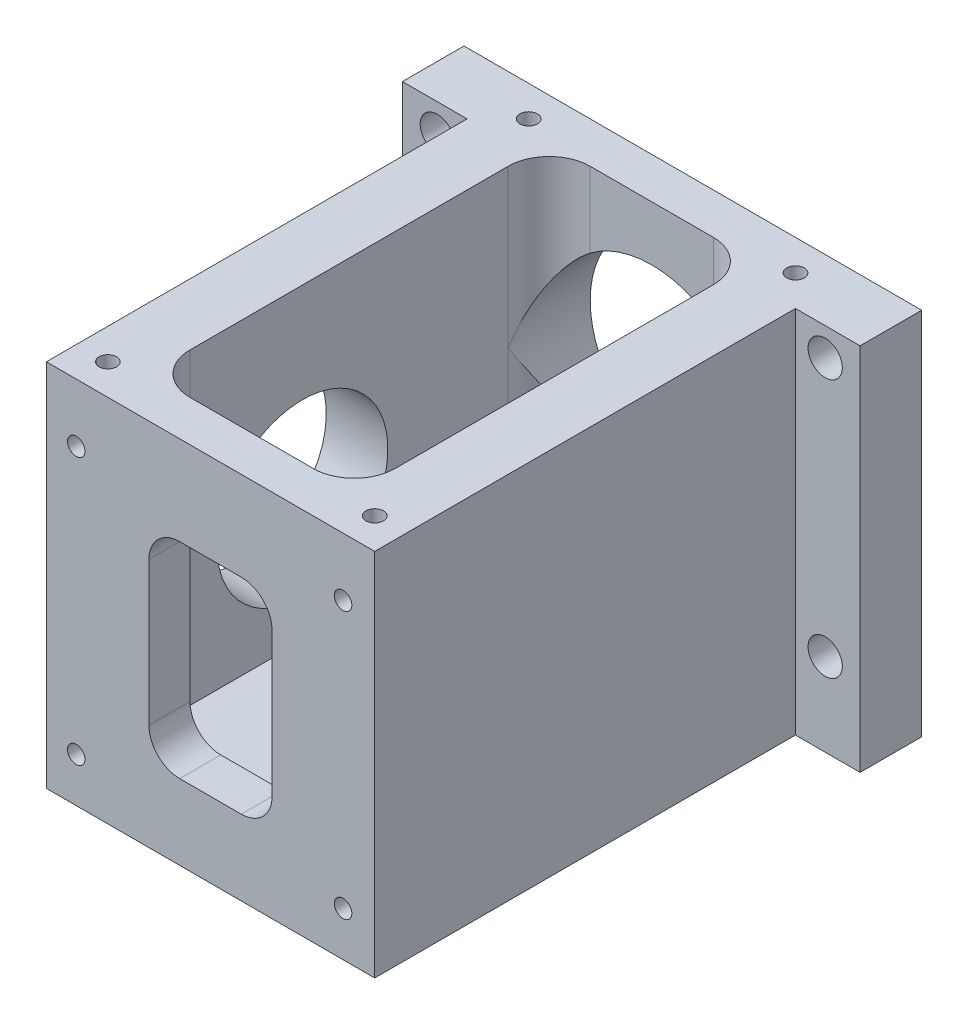
SolidWorks part; units mm, degrees
ref_plane "Front Plane" through (0, 0, 0) normal (0, 0, 1) x (1, 0, 0)
ref_plane "Top Plane" through (0, 0, 0) normal (0, 1, 0) x (1, 0, 0)
ref_plane "Right Plane" through (0, 0, 0) normal (1, 0, 0) x (0, 0, -1)
sketch "Sketch1" plane through (0, 0, 0) normal (0, 1, 0) x (1, 0, 0)
  line L1 (-25.4, -37.3063) -> (25.4, -37.3063)
  line L2 (-25.4, -37.3063) -> (-25.4, 37.3062)
  line L3 (-25.4, 37.3062) -> (25.4, 37.3062)
  line L4 (25.4, -37.3063) -> (25.4, 37.3062)
  line L5 (-25.4, -37.3063) -> (25.4, 37.3062) construction
  line L6 (-25.4, 37.3062) -> (25.4, -37.3063) construction
  point P0 (0, 0)
  dimension "D1" = 50.8
  dimension "D2" = 74.6125
extrude "Boss-Extrude1" add sketch "Sketch1" along normal blind 57.15
sketch "Sketch2" plane through (0, 57.15, 0) normal (0, 1, 0) x (1, 0, 0)
  line L0 (25.4, 37.3062) -> (-25.4, 37.3062) construction
  line L1 (-15.875, -30.9562) -> (15.875, -30.9562)
  line L2 (-15.875, -30.9562) -> (-15.875, 30.9562)
  line L3 (-15.875, 30.9562) -> (15.875, 30.9562)
  line L4 (15.875, -30.9562) -> (15.875, 30.9562)
  line L5 (-15.875, -30.9562) -> (15.875, 30.9562) construction
  line L6 (-15.875, 30.9562) -> (15.875, -30.9562) construction
  line L7 (25.4, -37.3063) -> (25.4, 37.3062) construction
  point P0 (0, 0)
  dimension "D1" = 6.35
  dimension "D2" = 9.525
extrude "Cut-Extrude1" cut sketch "Sketch2" against normal offset from surface (47.625 mm away) 9.525 up to face at (0, 0, 0)
fillet "Fillet1" radius 6.35 4 edges at (-15.875, 33.3375, 30.9562) (15.875, 33.3375, 30.9562) (15.875, 33.3375, -30.9562) (-15.875, 33.3375, -30.9562)
ref_plane "Plane1" through (0, 9.525, 0) normal (0, 1, 0) x (-1, 0, 0)
sketch "Sketch3" plane through (0, 0, -37.3062) normal (0, 0, -1) x (-1, 0, 0)
  line L1 (17.4625, 9.525) -> (-17.4625, 9.525) construction
  circle A0 centre (0, 32.825) radius 15.875
  dimension "D1" = 31.75
  dimension "D2" = 23.3
extrude "Cut-Extrude2" cut sketch "Sketch3" against normal up to next
hole_wizard "#6-32 Tapped Hole1" positions "Sketch7" profile "Sketch6" tap size "#6-32" standard "Ansi Inch"
sketch "Sketch7" plane through (0, 57.15, 0) normal (0, 1, 0) x (-1, 0, 0)
  line L0 (-25.4, -37.3062) -> (25.4, -37.3062) construction
  line L1 (25.4, -37.3062) -> (25.4, 37.3063) construction
  line L2 (-25.4, 37.3063) -> (-25.4, -37.3062) construction
  line L3 (25.4, 37.3063) -> (-25.4, 37.3063) construction
  point P0 (20.6375, -32.5437)
  point P1 (-20.6375, -32.5437)
  point P3 (20.6375, 32.5438)
  point P5 (-20.6375, 32.5438)
  dimension "D1" = 4.7625
  dimension "D2" = 4.7625
  dimension "D3" = 4.7625
  dimension "D4" = 4.7625
sketch "Sketch6" plane through (-20.6375, 57.15, -32.5437) normal (1, 0, 0) x (0, 0, 1)
  line L0 (0, 0) -> (0, 8.4327)
  line L1 (0, 8.4327) -> (1.3525, 7.62)
  line L2 (1.3525, 7.62) -> (1.3525, 0)
  line L5 (1.3525, 0) -> (0, 0)
  line L10 (0, 8.4327) -> (-1.3526, 7.62) construction
  line L11 (0, -6.35) -> (0, 107.95) construction
  dimension "Tap Drill Dia." = 2.7051
  dimension "Tap Drill Depth" = 7.62
  dimension "Drill Angle" = 118
sketch "Sketch8" plane through (-25.4, 0, 0) normal (-1, 0, 0) x (0, 0, 1)
  line L0 (-37.3062, 0) -> (37.3063, 0) construction
  line L1 (-37.3062, 57.15) -> (-27.7812, 57.15)
  line L2 (-37.3062, 57.15) -> (-37.3062, 0)
  line L3 (-37.3062, 0) -> (-27.7812, 0)
  line L4 (-27.7812, 57.15) -> (-27.7812, 0)
  dimension "D1" = 9.525
extrude "Boss-Extrude2" add sketch "Sketch8" along normal blind 10
mirror "Mirror1" about plane through (0, 0, 0) normal (1, 0, 0) of "Boss-Extrude2"
hole_wizard "M5 Clearance Hole1" positions "Sketch10" profile "Sketch9" hole size "M5" standard "Ansi Metric" end condition up to next
sketch "Sketch10" plane through (0, 0, -37.3062) normal (0, 0, -1) x (-1, 0, 0)
  line L0 (-35.4, 0) -> (35.4, 0) construction
  line L3 (0, 64.6862) -> (0, -21.5166) construction
  point P0 (30, 12.827)
  point P1 (30, 52.827)
  point P3 (-30, 52.827)
  point P5 (-30, 12.827)
  dimension "D1" = 12.827
  dimension "D2" = 30
  dimension "D3" = 30
  dimension "D4" = 40
sketch "Sketch9" plane through (-30, 12.827, -37.3062) normal (1, 0, 0) x (0, 1, 0)
  line L0 (0, 0) -> (0, 9.525)
  line L1 (0, 9.525) -> (2.65, 9.525)
  line L2 (2.65, 9.525) -> (2.65, 0)
  line L5 (2.65, 0) -> (0, 0)
  line L11 (0, -6.35) -> (0, 107.95) construction
  dimension "Thru Hole Dia." = 5.3
  dimension "Thru Hole Depth" = 9.525
sketch "Sketch11" plane through (-25.4, 0, 0) normal (-1, 0, 0) x (0, 0, 1)
  line L0 (37.3063, 57.15) -> (37.3063, 0) construction
  circle A0 centre (7.2073, 28.575) radius 30.099 construction
  circle A1 centre (7.2073, 28.575) radius 13.208
  point P4 (37.3063, 28.575)
  dimension "D1" = 60.198
  dimension "D2" = 26.416
extrude "Cut-Extrude3" cut sketch "Sketch11" against normal up to next
hole_wizard "#10-32 Tapped Hole2" positions "Sketch13" profile "Sketch12" tap size "#10-32" standard "Ansi Inch"
sketch "Sketch13" plane through (-25.4, 0, 0) normal (-1, 0, 0) x (0, 0, 1)
  circle A0 centre (7.2073, 28.575) radius 24.003 construction
  point P8 (-16.7957, 28.575)
  point P40 (-4.7942, 49.3622)
  point P41 (19.2088, 49.3622)
  point P42 (31.2103, 28.575)
  point P43 (19.2087, 7.7878)
  point P44 (-4.7943, 7.7878)
  dimension "D1" = 48.006
  dimension "D2" = 6
sketch "Sketch12" plane through (-25.4, 28.575, -16.7957) normal (0, 1, 0) x (0, 0, 1)
  line L0 (0, 0) -> (0, 6.0393)
  line L1 (0, 6.0393) -> (2.0193, 4.826)
  line L2 (2.0193, 4.826) -> (2.0193, 0)
  line L5 (2.0193, 0) -> (0, 0)
  line L10 (0, 6.0393) -> (-2.0193, 4.826) construction
  line L11 (0, -6.35) -> (0, 107.95) construction
  dimension "Tap Drill Dia." = 4.0386
  dimension "Tap Drill Depth" = 4.826
  dimension "Drill Angle" = 118
hole_wizard "#2-56 Tapped Hole1" positions "Sketch16" profile "Sketch15" tap size "#2-56" standard "Ansi Inch"
sketch "Sketch16" plane through (0, 9.525, 0) normal (0, 1, 0) x (-1, 0, 0)
  point P1 (13, -12.1634)
  point P4 (13, -25.1634)
  point P7 (-13, -25.1634)
  point P10 (-13, -12.1634)
  point P15 (5.6515, 4.7437)
  point P18 (-5.6515, 4.7437)
sketch "Sketch15" plane through (-13, 9.525, -12.1634) normal (1, 0, 0) x (0, 0, 1)
  line L0 (0, 0) -> (0, 7.1382)
  line L1 (0, 7.1382) -> (0.889, 6.604)
  line L2 (0.889, 6.604) -> (0.889, 0)
  line L5 (0.889, 0) -> (0, 0)
  line L10 (0, 7.1382) -> (-0.889, 6.604) construction
  line L11 (0, -6.35) -> (0, 107.95) construction
  dimension "Tap Drill Dia." = 1.778
  dimension "Tap Drill Depth" = 6.604
  dimension "Drill Angle" = 118
sketch "Sketch21" plane through (0, 0, 37.3063) normal (0, 0, 1) x (1, 0, 0)
hole_wizard "#6-32 Tapped Hole2" positions "Sketch23" profile "Sketch22" tap size "#6-32" standard "Ansi Inch"
sketch "Sketch23" plane through (0, 0, 37.3063) normal (0, 0, 1) x (1, 0, 0)
  point P1 (20.5062, 48.141)
  point P3 (20.5062, 6.866)
  point P5 (-20.7688, 48.141)
  point P7 (-20.7688, 6.866)
sketch "Sketch22" plane through (20.5062, 48.141, 37.3063) normal (1, 0, 0) x (0, -1, 0)
  line L0 (0, 0) -> (0, 9.8551)
  line L1 (0, 9.8551) -> (1.3525, 9.0424)
  line L2 (1.3525, 9.0424) -> (1.3525, 0)
  line L5 (1.3525, 0) -> (0, 0)
  line L10 (0, 9.8551) -> (-1.3526, 9.0424) construction
  line L11 (0, -6.35) -> (0, 107.95) construction
  dimension "Tap Drill Dia." = 2.7051
  dimension "Tap Drill Depth" = 9.0424
  dimension "Drill Angle" = 118
sketch "Sketch24" plane through (0, 0, 37.3063) normal (0, 0, 1) x (1, 0, 0)
  line L0 (-4.7625, 11.6285) -> (4.7625, 11.6285)
  line L1 (-9.525, 16.391) -> (-9.525, 38.616)
  line L2 (-4.7625, 43.3785) -> (4.7625, 43.3785)
  line L3 (9.525, 16.391) -> (9.525, 38.616)
  line L4 (-9.525, 11.6285) -> (9.525, 43.3785) construction
  line L5 (-9.525, 43.3785) -> (9.525, 11.6285) construction
  line L8 (-25.4, 0) -> (25.4, 0) construction
  line L9 (-20.7688, 48.141) -> (-20.7688, 6.866) construction
  arc A0 (-4.7625, 11.6285) -> (-9.525, 16.391) centre (-4.7625, 16.391) cw
  arc A1 (4.7625, 11.6285) -> (9.525, 16.391) centre (4.7625, 16.391) ccw
  arc A2 (4.7625, 43.3785) -> (9.525, 38.616) centre (4.7625, 38.616) cw
  arc A3 (-9.525, 38.616) -> (-4.7625, 43.3785) centre (-4.7625, 38.616) cw
  point P0 (0, 27.5035)
  point P19 (0, 0)
  point P20 (-20.7688, 27.5035)
  dimension "D2" = 4.7625
  dimension "D1" = 31.75
  dimension "D3" = 19.05
extrude "Cut-Extrude6" cut sketch "Sketch24" against normal up to next
